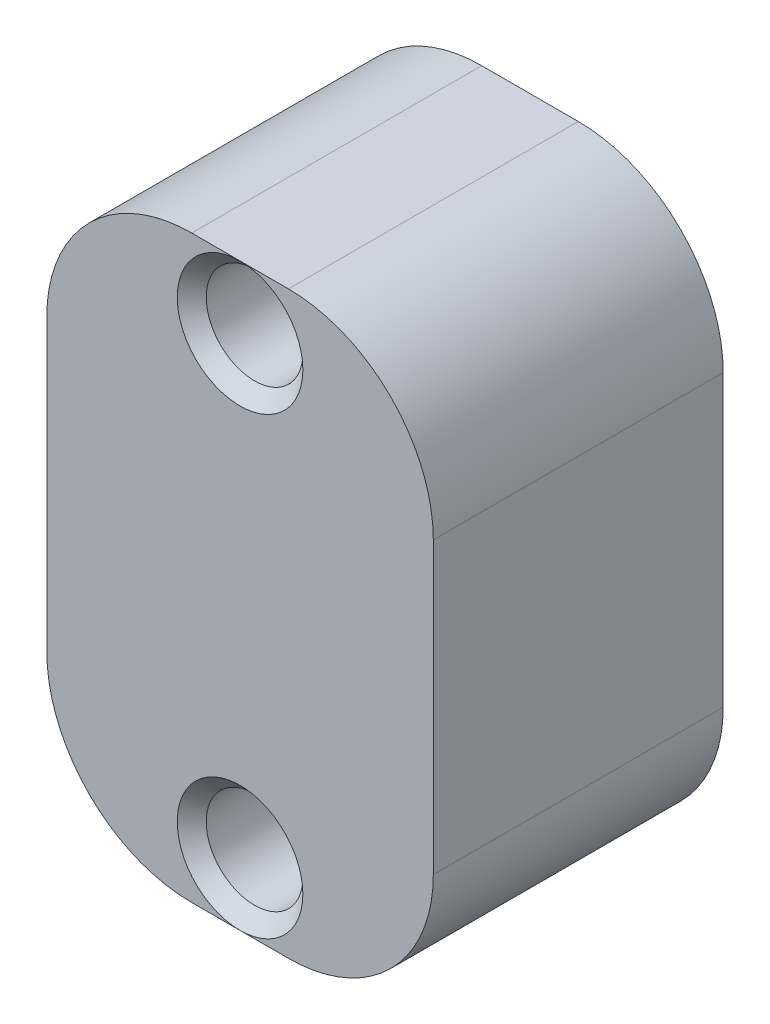
SolidWorks part; units mm, degrees
note: The reader was unsure of these and kept them because the rebuilt part matched: thickness of "Brida base1", "Chapa metálica4", "Chapa metálica(5)".
material "aluminio"
ref_plane "Alzado" through (0, 0, 0) normal (0, 0, 1) x (1, 0, 0)
ref_plane "Planta" through (0, 0, 0) normal (0, 1, 0) x (1, 0, 0)
ref_plane "Vista lateral" through (0, 0, 0) normal (1, 0, 0) x (0, 0, -1)
sketch "Croquis1" plane through (0, 0, 0) normal (0, 0, 1) x (1, 0, 0)
  line L0 (0, 30) -> (0, 18)
  line L1 (0, 30) -> (20, 30)
  line L2 (20, 30) -> (20, 0)
  line L3 (20, 0) -> (0, 0)
  line L4 (0, 15) -> (14, 15) construction
  line L5 (14, 15) -> (6, 15) construction
  line L6 (14, 12) -> (0, 12)
  line L7 (14, 18) -> (0, 18)
  line L8 (0, 12) -> (0, 0)
  arc A0 (14, 12) -> (14, 18) centre (14, 15) ccw
  circle A1 centre (10, 3.25) radius 2.5
  circle A6 centre (10, 26.75) radius 2.5
  point P6 (10, 15)
  dimension "D3" = 4
  dimension "D4" = 10
  dimension "D9" = 23.5
  dimension "D10" = 5
  dimension "D6" = 6
  dimension "D1" = 20
  dimension "D2" = 30
base flange "Brida base1" sketch "Croquis1" thickness 15 reverse thickness direction no parameters "D1"=1
ref_plane "Plano1" through (0, 15, 0) normal (0, 1, 0) x (1, 0, 0)
fillet "Redondeo1" radius 7.5 4 edges at (20, 0, -7.5) (20, 30, -7.5) (0, 30, -7.5) (0, 0, -7.5)
chamfer "Chaflán1" distance 0.75 angle 45 7 edges at (12.5, 26.75, -15) (7, 12, -15) (17, 15, -15) (7, 18, -15) (7.5, 3.25, -15) (7.5, 3.25, 0) (12.5, 26.75, 0)
sketch "Croquis2" plane through (0, 0, 0) normal (0, 0, -1) x (-1, 0, 0)
  line L0 (0, 18) -> (-14, 18) construction
  line L1 (-14, 12) -> (0, 12) construction
  line L2 (0, 18) -> (-14, 18)
  line L3 (-14, 12) -> (0, 12)
  line L4 (0, 18) -> (0, 12)
  arc A1 (-14, 18) -> (-14, 12) centre (-14, 15) ccw
  arc A2 (-14, 18) -> (-14, 12) centre (-14, 15) ccw construction
extrude "Saliente-Extruir1" add sketch "Croquis2" along normal blind 5
fillet "Redondeo2" radius 1 3 edges at (7, 12, -5) (17, 15, -5) (7, 18, -5)
sketch "Líneas de pliegue1" plane through (0, 0, 0) normal (0, 1, 0) x (1, 0, 0)
sketch "Cuadro delimitador1" plane through (0, 0, 0) normal (0, 1, 0) x (1, 0, 0)
sheet metal parameters "Chapa metálica4" thickness 15 parameters "D1"=1
flat pattern "Chapa desplegada4" [suppressed]
sketch "Líneas de pliegue2" plane through (0, 0, 0) normal (0, 1, 0) x (1, 0, 0)
sketch "Cuadro delimitador2" [suppressed] plane through (0, 0, 0) normal (0, 1, 0) x (1, 0, 0)
sheet metal parameters "Chapa metálica(5)" thickness 15 parameters "D1"=1, "D7"=12
flat pattern "Chapa desplegada4"
sketch "Líneas de pliegue2" plane through (0, 0, 0) normal (0, 1, 0) x (1, 0, 0)
sketch3d "Cuadro delimitador2" [suppressed]
  line L0 (6, -15, 0) -> (6, 15, 0) construction
  line L1 (-14, -15, 0) -> (-14, 15, 0) construction
  line L2 (6, -15, 0) -> (-14, -15, 0) construction
  line L3 (6, 15, 0) -> (-14, 15, 0) construction
